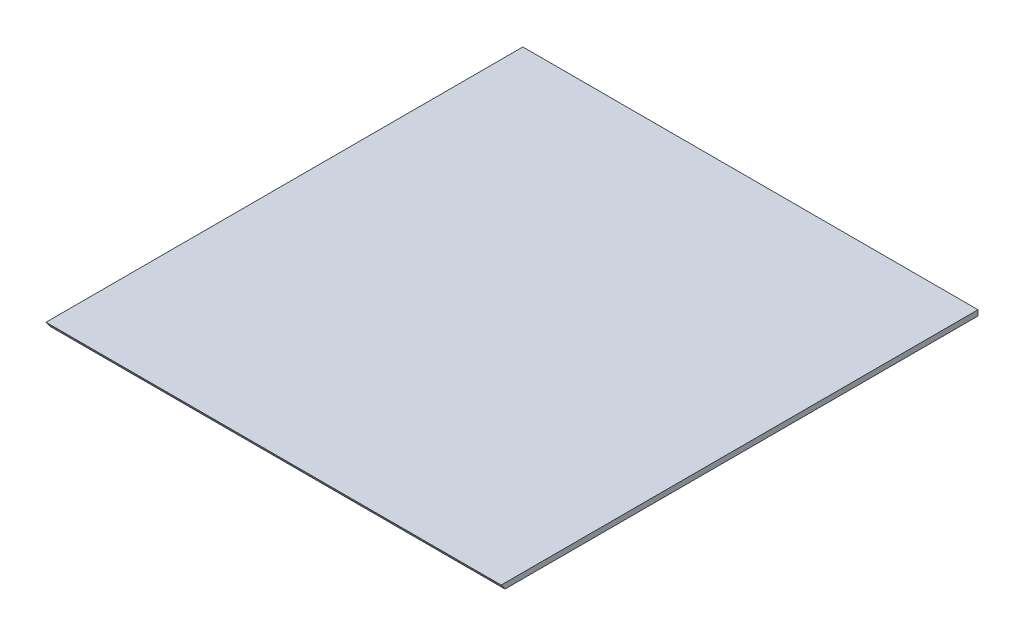
SolidWorks part; units mm, degrees
ref_plane "Front Plane" through (0, 0, 0) normal (0, 0, 1) x (1, 0, 0)
ref_plane "Top Plane" through (0, 0, 0) normal (0, 1, 0) x (1, 0, 0)
ref_plane "Right Plane" through (0, 0, 0) normal (1, 0, 0) x (0, 0, -1)
sketch "Sketch1" plane through (0, 0, 0) normal (0, 1, 0) x (1, 0, 0)
  line L1 (-133.35, -139.7) -> (133.35, -139.7)
  line L2 (-133.35, -139.7) -> (-133.35, 139.7)
  line L3 (-133.35, 139.7) -> (133.35, 139.7)
  line L4 (133.35, -139.7) -> (133.35, 139.7)
  line L5 (-133.35, -139.7) -> (133.35, 139.7) construction
  line L6 (-133.35, 139.7) -> (133.35, -139.7) construction
  point P0 (0, 0)
extrude "Boss-Extrude1" add sketch "Sketch1" along normal mid plane 3.175 contours L2 L3 L4 L1
sketch "Sketch2" plane through (-133.35, 0, 0) normal (-1, 0, 0) x (0, 0, 1)
  line L1 (139.7, 1.5875) -> (137.4471, -1.5875)
  line L2 (139.7, -1.5875) -> (-139.7, -1.5875) construction
  line L4 (137.4471, -1.5875) -> (139.4026, -2.9751)
  line L6 (139.4026, -2.9751) -> (141.6555, 0.1999)
  line L7 (141.6555, 0.1999) -> (139.7, 1.5875)
extrude "Cut-Extrude4" cut sketch "Sketch2" against normal through all contours L1 L4 L6 L7
